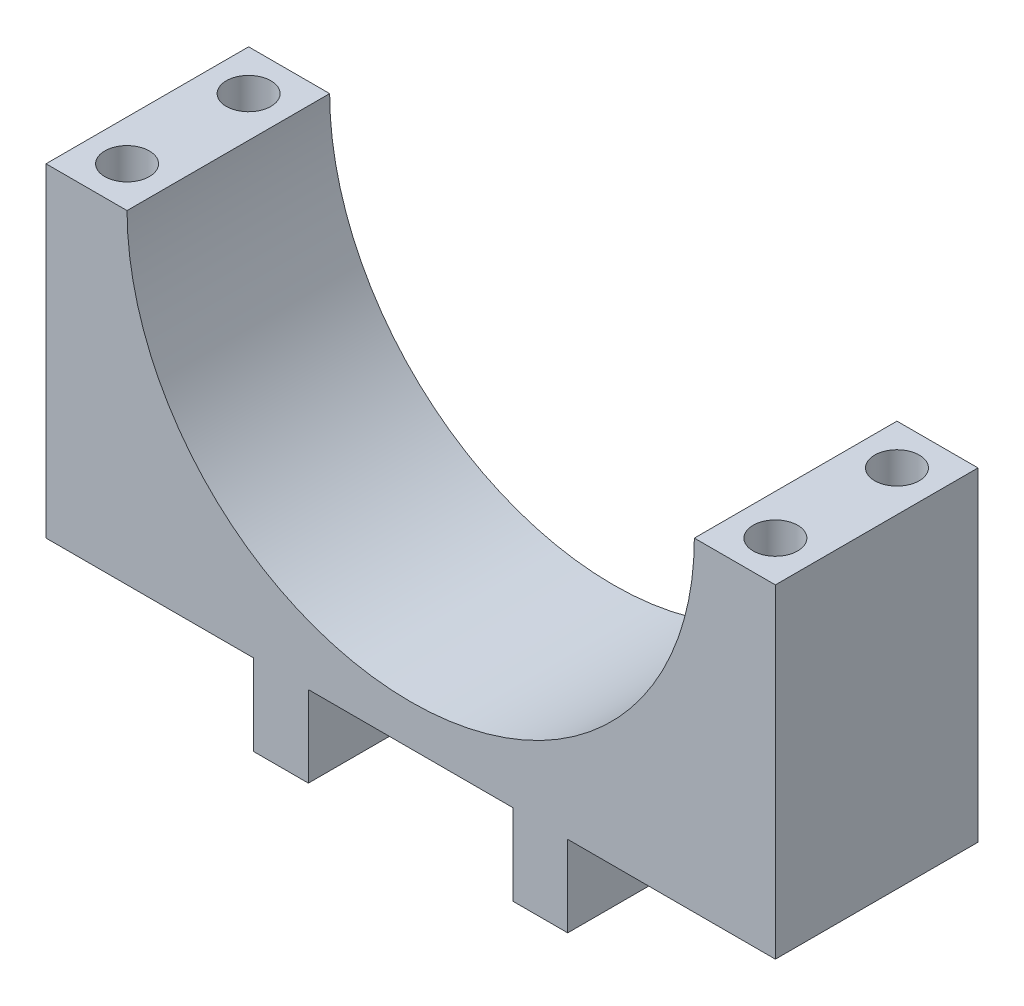
SolidWorks part; units mm, degrees
ref_plane "Płaszczyzna przednia" through (0, 0, 0) normal (0, 0, 1) x (1, 0, 0)
ref_plane "Płaszczyzna górna" through (0, 0, 0) normal (0, 1, 0) x (1, 0, 0)
ref_plane "Płaszczyzna prawa" through (0, 0, 0) normal (1, 0, 0) x (0, 0, -1)
sketch "Szkic1" plane through (0, 0, 0) normal (0, 0, 1) x (1, 0, 0)
  line L0 (70, 0) -> (90, 0)
  line L1 (90, 0) -> (90, -80)
  line L2 (90, -80) -> (38.75, -80)
  line L3 (38.75, -80) -> (38.75, -100)
  line L4 (38.75, -100) -> (25.25, -100)
  line L5 (25.25, -100) -> (25.25, -80)
  line L6 (25.25, -80) -> (-25.25, -80)
  line L7 (-25.25, -80) -> (-25.25, -100)
  line L8 (-25.25, -100) -> (-38.75, -100)
  line L9 (-38.75, -100) -> (-38.75, -80)
  line L10 (-38.75, -80) -> (-90, -80)
  line L11 (-90, -80) -> (-90, 0)
  line L12 (-90, 0) -> (-70, 0)
  line L13 (0, 27.9886) -> (0, -166.5804) construction
  arc A0 (70, 0) -> (-70, 0) centre (0, 0) cw
  point P19 (0, -80)
  dimension "D1" = 70
  dimension "D2" = 13.5
  dimension "D3" = 13.5
  dimension "D4" = 50.5
  dimension "D5" = 20
  dimension "D6" = 80
  dimension "D7" = 20
  dimension "D8" = 20
extrude "Dodanie-wyciągnięcie1" add sketch "Szkic1" along normal blind 50
ref_plane "Płaszczyzna1" through (0, 0, 0) normal (0, 1, 0) x (1, 0, 0)
sketch "Szkic2" plane through (0, 0, 0) normal (0, 1, 0) x (1, 0, 0)
  line L0 (-70, 0) -> (-90, 0) construction
  line L1 (-90, -50) -> (-90, 0) construction
  line L2 (-70, -50) -> (-90, -50) construction
  circle A0 centre (-80, -10) radius 5.5
  circle A1 centre (-80, -40) radius 5.5
  dimension "D1" = 10
  dimension "D3" = 10
  dimension "D2" = 10
  dimension "D4" = 10
extrude "Wytnij-wyciągnięcie1" cut sketch "Szkic2" against normal blind 21
mirror "Lustro1" about plane through (0, 0, 0) normal (1, 0, 0) of "Wytnij-wyciągnięcie1"
